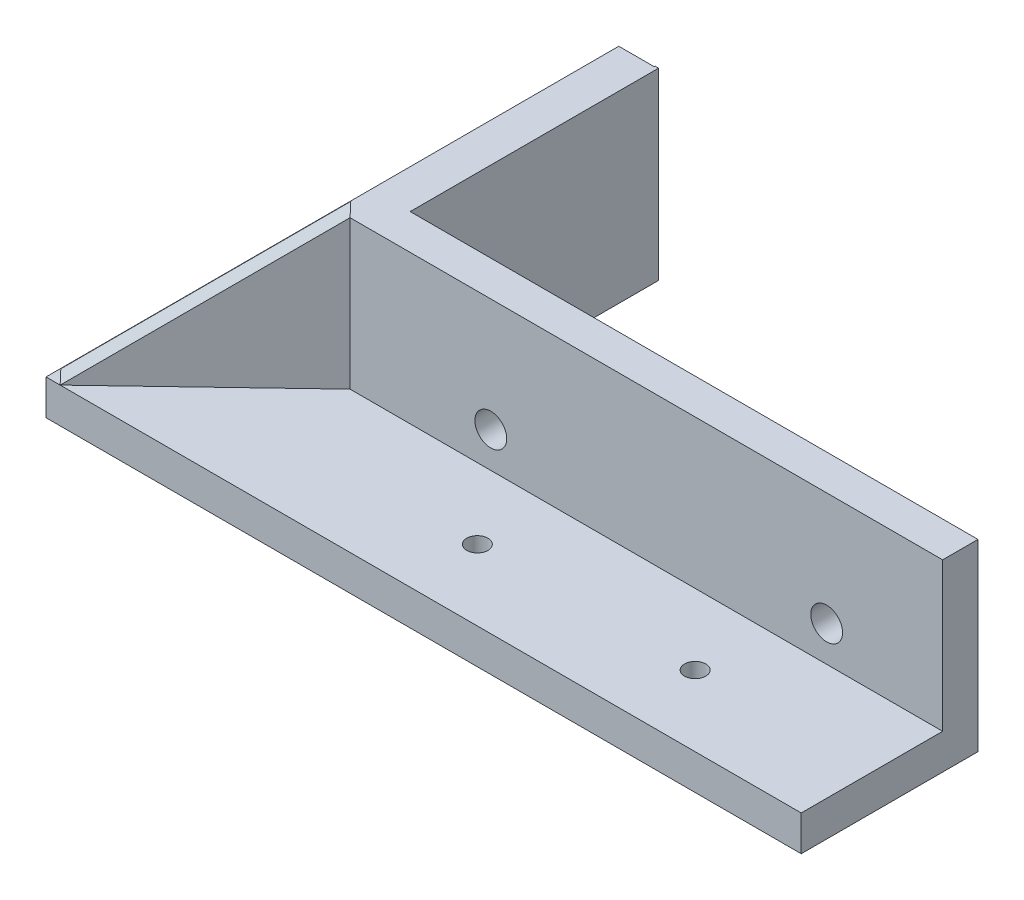
SolidWorks part; units mm, degrees
ref_plane "Front Plane" through (0, 0, 0) normal (0, 0, 1) x (1, 0, 0)
ref_plane "Top Plane" through (0, 0, 0) normal (0, 1, 0) x (1, 0, 0)
ref_plane "Right Plane" through (0, 0, 0) normal (1, 0, 0) x (0, 0, -1)
sketch "Croquis1" plane through (0, 0, 0) normal (0, 1, 0) x (1, 0, 0)
  line L0 (-40.4, -2.5) -> (-40.4, 2.5)
  line L1 (-40.4, -2.5) -> (40.4, -2.5)
  line L2 (-40.4, 2.5) -> (40.4, 2.5)
  line L3 (40.4, -2.5) -> (40.4, 2.5)
  line L4 (-40.4, -2.5) -> (40.4, 2.5) construction
  line L5 (-40.4, 2.5) -> (40.4, -2.5) construction
  line L6 (-40.4, -2.5) -> (-40.4, -22.5)
  line L7 (-40.4, -22.5) -> (40.4, -22.5)
  line L8 (40.4, -22.5) -> (40.4, -2.5)
  line L9 (-40.4, 2.5) -> (-40.4, 37.5)
  line L10 (-45.4, 37.5) -> (-45.4, -2.5)
  line L11 (-45.4, -2.5) -> (-40.4, -2.5)
  line L12 (-40.4, 37.5) -> (-66.4, 37.5)
  line L13 (-66.4, 37.5) -> (-66.4, -22.5)
  line L14 (-66.4, -22.5) -> (-40.4, -22.5)
  line L15 (0, 0) -> (0, 33.4342) construction
  line L16 (45.4, -2.5) -> (40.4, -2.5)
  line L17 (66.4, -22.5) -> (40.4, -22.5)
  line L18 (66.4, 37.5) -> (66.4, -22.5)
  line L19 (40.4, 37.5) -> (66.4, 37.5)
  line L20 (45.4, 37.5) -> (45.4, -2.5)
  line L21 (40.4, 37.5) -> (40.4, 2.5)
  circle A0 centre (-15.4, -12.5) radius 1.5
  circle A2 centre (-55.4, 12.5) radius 1.5
  circle A3 centre (15.4, -12.5) radius 1.5
  circle A4 centre (55.4, 12.5) radius 1.5
  point P1 (0, 0)
  dimension "D9" = 3
  dimension "D11" = 3
  dimension "D1" = 80.8
  dimension "D2" = 5
  dimension "D3" = 20
  dimension "D4" = 26
  dimension "D5" = 5
  dimension "D6" = 40
  dimension "D7" = 25
  dimension "D13" = 10
  dimension "D14" = 10
  dimension "D15" = 25
extrude "Saliente-Extruir1" add sketch "Croquis1" along normal blind 5 contours L7 L8 L1 L6 | L1 L3 L2 L0 region at (0, 0, 0) region at (0, 0, 12.5)
extrude "Saliente-Extruir2" add sketch "Croquis1<3>" along normal blind 26 contours L1 L3 L2 L0 region at (0, 0, 0)
sketch "Croquis1<3>" plane through (0, 0, 0) normal (0, 1, 0) x (1, 0, 0) same geometry as "Croquis1"
extrude "Saliente-Extruir3" add sketch "Croquis1<4>" along normal blind 5 contours L9 L12 L10 L11 L0 | L13 L14 L6 L11 L10 L12 A2 | L19 L20 L16 L8 L17 L18 A4 | L19 L21 L3 L16 L20 region at (-42.9, 0, -17.5) region at (-54.9417, 0, -5.9956) region at (54.9417, 0, -5.9956) region at (42.9, 0, -17.5)
sketch "Croquis1<4>" plane through (0, 0, 0) normal (0, 1, 0) x (1, 0, 0) same geometry as "Croquis1"
extrude "Saliente-Extruir4" add sketch "Croquis1<5>" along normal blind 26 contours L9 L12 L10 L11 L0 | L19 L21 L3 L16 L20 region at (-42.9, 0, -17.5) region at (42.9, 0, -17.5)
sketch "Croquis1<5>" plane through (0, 0, 0) normal (0, 1, 0) x (1, 0, 0) same geometry as "Croquis1"
sketch "Croquis3" plane through (0, 0, 2.5) normal (0, 0, 1) x (1, 0, 0)
  line L0 (45.4, 5) -> (-45.4, 5) construction
  line L1 (-45.4, 26) -> (-45.4, 5) construction
  line L2 (45.4, 26) -> (45.4, 5) construction
  circle A0 centre (-23.5, 10) radius 2.25
  circle A1 centre (24, 10) radius 2.25
  dimension "D5" = 4.5
  dimension "D6" = 4.5
  dimension "D1" = 5
  dimension "D2" = 5
  dimension "D3" = 21.9
  dimension "D4" = 21.4
extrude "Cortar-Extruir1" cut sketch "Croquis3" against normal blind 26
sketch "Croquis4" plane through (0, 5, 0) normal (0, 1, 0) x (1, 0, 0)
  line L0 (-45.4, -0.5) -> (-45.4, -2.5)
  line L1 (-45.4, -2.5) -> (-45.4, 37.5) construction
  line L2 (-45.4, -2.5) -> (-43.4, -2.5)
  line L3 (45.4, -2.5) -> (-45.4, -2.5) construction
  line L4 (-43.4, -2.5) -> (-64.4, -22.5)
  line L5 (-66.4, -22.5) -> (66.4, -22.5) construction
  line L6 (-64.4, -22.5) -> (-66.4, -22.5)
  line L7 (-66.4, -22.5) -> (-66.4, -20.5)
  line L8 (-66.4, 37.5) -> (-66.4, -22.5) construction
  line L9 (-66.4, -20.5) -> (-45.4, -0.5)
  dimension "D1" = 2
  dimension "D2" = 2
  dimension "D3" = 2
  dimension "D4" = 2
extrude "Saliente-Extruir5" add sketch "Croquis4" along normal blind 21
sketch "Croquis5" plane through (-19.3936, 0, -20.3633) normal (0.6897, 0, 0.7241) x (0.7241, 0, -0.6897)
  line L0 (-62.1517, 5) -> (-33.1517, 26)
  line L1 (-33.1517, 26) -> (-26.4869, 30.8262)
  line L2 (-26.4869, 30.8262) -> (-82.7596, 33.4038)
  line L3 (-82.7596, 33.4038) -> (-84.0606, 5)
  line L4 (-84.0606, 5) -> (-62.1517, 5)
extrude "Cortar-Extruir2" cut sketch "Croquis5" against normal blind 21
mirror "Simetría1" about plane through (0, 0, 0) normal (1, 0, 0) of "Saliente-Extruir5"
mirror "Simetría2" about plane through (0, 0, 0) normal (1, 0, 0) of "Cortar-Extruir2"
sketch "Croquis7" plane through (0, 0, -37.5) normal (0, 0, -1) x (-1, 0, 0)
  line L0 (-40.4, 0) -> (-40.4, 40.2261)
  line L1 (-40.4, 40.2261) -> (-77.282, 40.2261)
  line L2 (-77.282, 40.2261) -> (-77.282, 0)
  line L3 (-77.282, 0) -> (-40.4, 0)
extrude "Cortar-Extruir3" cut sketch "Croquis7" against normal blind 90
sketch "Croquis8" plane through (-40.4, 0, 0) normal (1, 0, 0) x (0, 0, -1)
  line L0 (37.6292, 0) -> (37.6292, 26)
  line L1 (37.6292, 0) -> (2.3708, 0)
  line L2 (37.6292, 26) -> (2.3708, 26)
  line L3 (2.3708, 0) -> (2.3708, 26)
  line L4 (37.6292, 0) -> (2.3708, 26) construction
  line L5 (37.6292, 26) -> (2.3708, 0) construction
  point P1 (20, 13)
extrude "Saliente-Extruir6" add sketch "Croquis8" along normal blind 0.5
